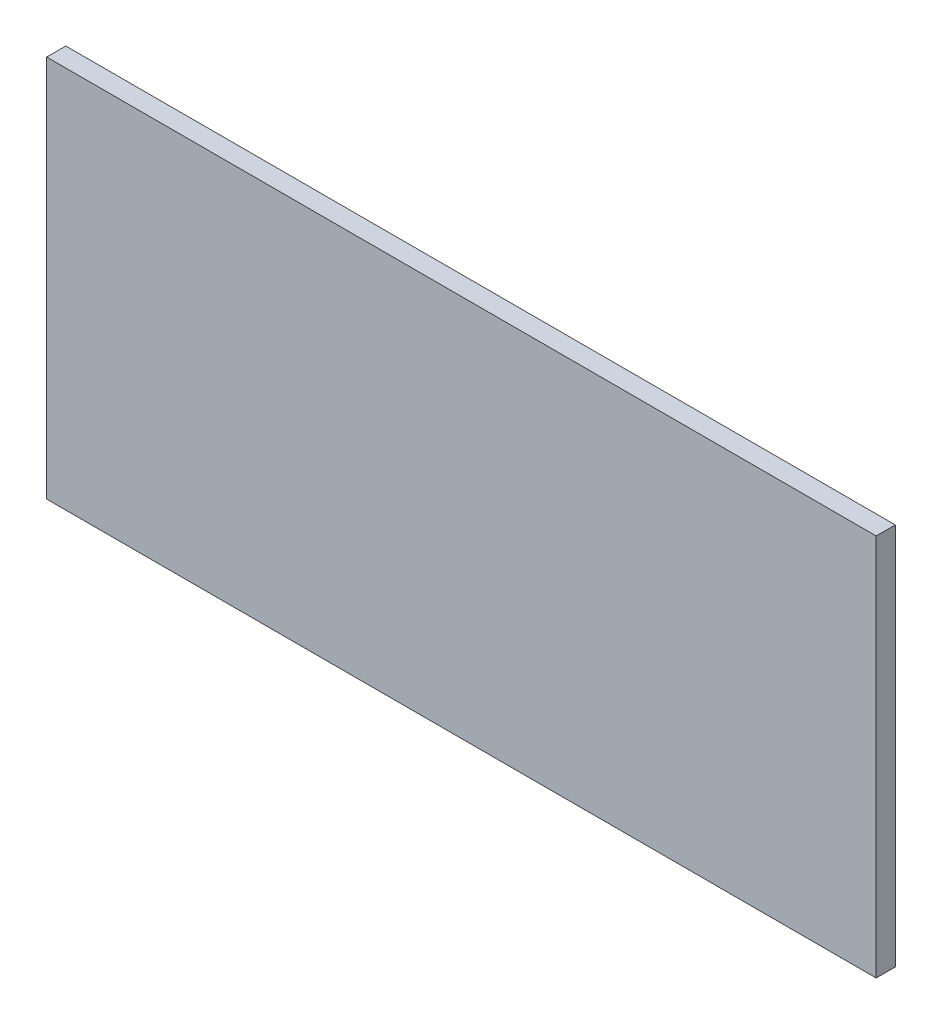
SolidWorks part; units mm, degrees
ref_plane "Front Plane" through (0, 0, 0) normal (0, 0, 1) x (1, 0, 0)
ref_plane "Top Plane" through (0, 0, 0) normal (0, 1, 0) x (1, 0, 0)
ref_plane "Right Plane" through (0, 0, 0) normal (1, 0, 0) x (0, 0, -1)
sketch "Sketch1" plane through (0, 0, 0) normal (0, 0, 1) x (1, 0, 0)
  line L0 (103.2793, 27.8614) -> (103.2793, 8.8614) construction
  line L1 (78.2793, 27.8614) -> (128.2793, 27.8614) construction
  line L2 (128.2793, 8.8614) -> (78.2793, 8.8614) construction
  line L3 (70.7793, 33.3614) -> (70.7793, 3.3614) construction
  line L5 (135.7793, 3.3614) -> (135.7793, 33.3614) construction
  line L6 (135.7793, 33.3614) -> (70.7793, 33.3614) construction
  line L7 (70.7793, 33.3614) -> (70.7793, 3.3614) construction
  line L8 (135.7793, 3.3614) -> (70.7793, 33.3614) construction
  line L9 (135.7793, 33.3614) -> (70.7793, 3.3614) construction
  line L12 (135.7793, 33.3614) -> (70.7793, 33.3614) construction
  line L13 (70.7793, 3.3614) -> (70.7793, 33.3614)
  line L14 (70.7793, 33.3614) -> (135.7793, 33.3614)
  line L15 (135.7793, 33.3614) -> (135.7793, 3.3614)
  line L16 (135.7793, 3.3614) -> (70.7793, 3.3614)
  point P6 (103.2793, 18.3614)
  dimension "D1" = 65
  dimension "D2" = 30
extrude "Boss-Extrude1" add sketch "Sketch1" against normal blind 1.5
sketch "Sketch2" plane through (0, 0, -1.5) normal (0, 0, -1) x (-1, 0, 0)
  line L0 (-128.2793, 25.3614) -> (-78.2793, 25.3614) construction
  line L1 (-128.2793, 8.8614) -> (-128.2793, 27.8614) construction
  line L2 (-78.2793, 8.8614) -> (-78.2793, 27.8614) construction
  line L3 (-128.2793, 11.3614) -> (-78.2793, 11.3614) construction
  line L4 (-80.7793, 27.8614) -> (-80.7793, 8.8614) construction
  line L5 (-78.2793, 27.8614) -> (-128.2793, 27.8614) construction
  line L6 (-128.2793, 8.8614) -> (-78.2793, 8.8614) construction
  line L7 (-125.7793, 27.8614) -> (-125.7793, 8.8614) construction
  line L8 (-125.7793, 27.8614) -> (-80.7793, 27.8614)
  line L9 (-78.2793, 25.3614) -> (-78.2793, 11.3614)
  line L10 (-80.7793, 8.8614) -> (-125.7793, 8.8614)
  line L12 (-128.2793, 11.3614) -> (-128.2793, 25.3614)
  arc A0 (-128.2793, 25.3614) -> (-125.7793, 27.8614) centre (-125.7793, 25.3614) cw
  arc A1 (-80.7793, 27.8614) -> (-78.2793, 25.3614) centre (-80.7793, 25.3614) cw
  arc A2 (-80.7793, 8.8614) -> (-78.2793, 11.3614) centre (-80.7793, 11.3614) ccw
  arc A3 (-125.7793, 8.8614) -> (-128.2793, 11.3614) centre (-125.7793, 11.3614) cw
  dimension "D1" = 2.5
extrude "Boss-Extrude2" add sketch "Sketch2" along normal blind 1.5 separate body
